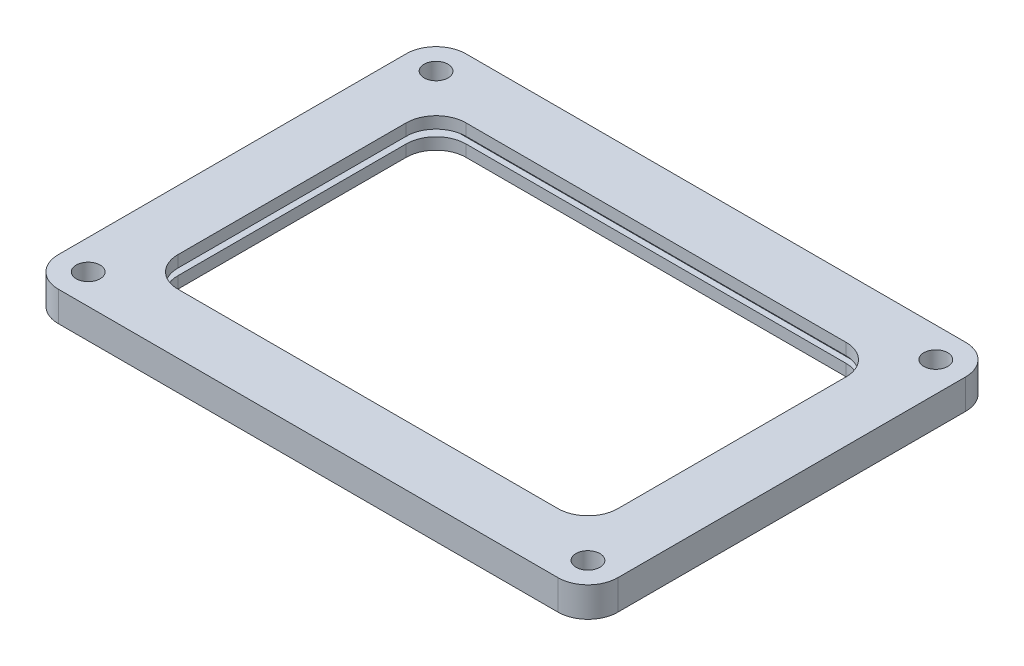
SolidWorks part; units mm, degrees
ref_plane "Front Plane" through (0, 0, 0) normal (0, 0, 1) x (1, 0, 0)
ref_plane "Top Plane" through (0, 0, 0) normal (0, 1, 0) x (1, 0, 0)
ref_plane "Right Plane" through (0, 0, 0) normal (1, 0, 0) x (0, 0, -1)
sketch "Sketch1" plane through (0, 0, 0) normal (0, 1, 0) x (1, 0, 0)
  line L0 (-36.79, 24.09) -> (36.79, 24.09)
  line L1 (-46.79, -34.09) -> (46.79, -34.09)
  line L2 (-46.79, -34.09) -> (-46.79, 34.09)
  line L3 (-46.79, 34.09) -> (46.79, 34.09)
  line L4 (46.79, -34.09) -> (46.79, 34.09)
  line L5 (-46.79, -34.09) -> (46.79, 34.09) construction
  line L6 (-46.79, 34.09) -> (46.79, -34.09) construction
  line L7 (36.79, -24.09) -> (36.79, 24.09)
  line L8 (-36.79, -24.09) -> (36.79, -24.09)
  line L9 (-36.79, -24.09) -> (-36.79, 24.09)
  line L10 (-31.79, 34.09) -> (-31.79, 24.09)
  line L11 (-46.79, 19.09) -> (-36.79, 19.09)
  line L12 (0, 34.09) -> (0, -34.09) construction
  line L13 (-46.79, 0) -> (46.79, 0) construction
  line L14 (-36.79, 24.09) -> (-46.79, 24.09)
  line L15 (-36.79, 24.09) -> (-36.79, 34.09)
  line L16 (-41.79, 34.09) -> (-41.79, -34.09) construction
  line L17 (-46.79, 29.09) -> (46.79, 29.09) construction
  line L18 (42.34, 34.09) -> (42.34, -34.09)
  line L19 (-42.34, 34.09) -> (-41.24, 34.09)
  line L20 (-42.34, 34.09) -> (-42.34, -34.09)
  line L21 (-42.34, -34.09) -> (-41.24, -34.09)
  line L22 (-41.24, 34.09) -> (-41.24, -34.09)
  line L23 (-46.79, 29.64) -> (46.79, 29.64)
  line L24 (-46.79, 29.64) -> (-46.79, 28.54)
  line L25 (-46.79, 28.54) -> (46.79, 28.54)
  line L26 (46.79, 29.64) -> (46.79, 28.54)
  line L27 (41.24, 34.09) -> (41.24, -34.09)
  line L28 (31.79, 34.09) -> (31.79, 24.09)
  line L29 (46.79, 19.09) -> (36.79, 19.09)
  line L30 (36.79, 24.09) -> (46.79, 24.09)
  line L31 (36.79, 24.09) -> (36.79, 34.09)
  line L32 (-31.79, -34.09) -> (-31.79, -24.09)
  line L33 (-36.79, -24.09) -> (-36.79, -34.09)
  line L34 (-36.79, -24.09) -> (-46.79, -24.09)
  line L35 (-46.79, -19.09) -> (-36.79, -19.09)
  line L36 (46.79, -19.09) -> (36.79, -19.09)
  line L37 (36.79, -24.09) -> (46.79, -24.09)
  line L38 (36.79, -24.09) -> (36.79, -34.09)
  line L39 (31.79, -34.09) -> (31.79, -24.09)
  line L40 (-46.79, -28.54) -> (46.79, -28.54)
  line L41 (-46.79, -29.64) -> (46.79, -29.64)
  circle A0 centre (-41.79, 29.09) radius 2
  circle A1 centre (41.79, 29.09) radius 2
  circle A2 centre (41.79, -29.09) radius 2
  circle A3 centre (-41.79, -29.09) radius 2
  point P0 (0, 0)
  point P22 (-41.79, 19.09)
  point P25 (-36.79, 29.09)
  point P30 (-41.79, -34.09)
  point P35 (46.79, 29.09)
  dimension "D8" = 4
  dimension "D1" = 93.58
  dimension "D2" = 68.18
  dimension "D4" = 15
  dimension "D5" = 15
  dimension "D6" = 1.1
  dimension "D7" = 1.1
  dimension "D3" = 10
extrude "Boss-Extrude1" add sketch "Sketch1" along normal blind 5 contours L4 L3 L2 L1
extrude "Cut-Extrude2" cut sketch "Sketch1<12>" along normal through all contours L9 L8 L7 L0 region at (0, 0, 0)
sketch "Sketch1<12>" plane through (0, 0, 0) normal (0, 1, 0) x (1, 0, 0) same geometry as "Sketch1"
fillet "Fillet1" radius 5 4 edges at (-46.79, 2.5, -34.09) (-46.79, 2.5, 34.09) (46.79, 2.5, -34.09) (46.79, 2.5, 34.09)
fillet "Fillet2" radius 5 4 edges at (36.79, 2.5, 24.09) (36.79, 2.5, -24.09) (-36.79, 2.5, 24.09) (-36.79, 2.5, -24.09)
extrude "Cut-Extrude3" cut sketch "Sketch1<13>" along normal through all contours A1 | A2 | A3 | A0
sketch "Sketch1<13>" plane through (0, 0, 0) normal (0, 1, 0) x (1, 0, 0) same geometry as "Sketch1"
sketch "Sketch2" plane through (-46.79, 0, 0) normal (-1, 0, 0) x (0, 0, 1)
  line L0 (-29.09, 2.5) -> (29.09, 2.5) construction
  line L1 (-29.09, 5) -> (-29.09, 0) construction
  line L4 (-25.09, 3.05) -> (25.09, 3.05)
  line L5 (-25.09, 3.05) -> (-25.09, 1.95)
  line L6 (-25.09, 1.95) -> (25.09, 1.95)
  line L7 (25.09, 3.05) -> (25.09, 1.95)
  line L9 (29.09, 0) -> (29.09, 5) construction
  point P4 (25.09, 2.5)
  point P10 (0, 0)
  dimension "D1" = 1.1
  dimension "D2" = 4
  dimension "D3" = 4
extrude "Cut-Extrude4" cut sketch "Sketch2" against normal offset from surface (88.58 mm away) 5 up to face at (46.79, 2.5, 0)
